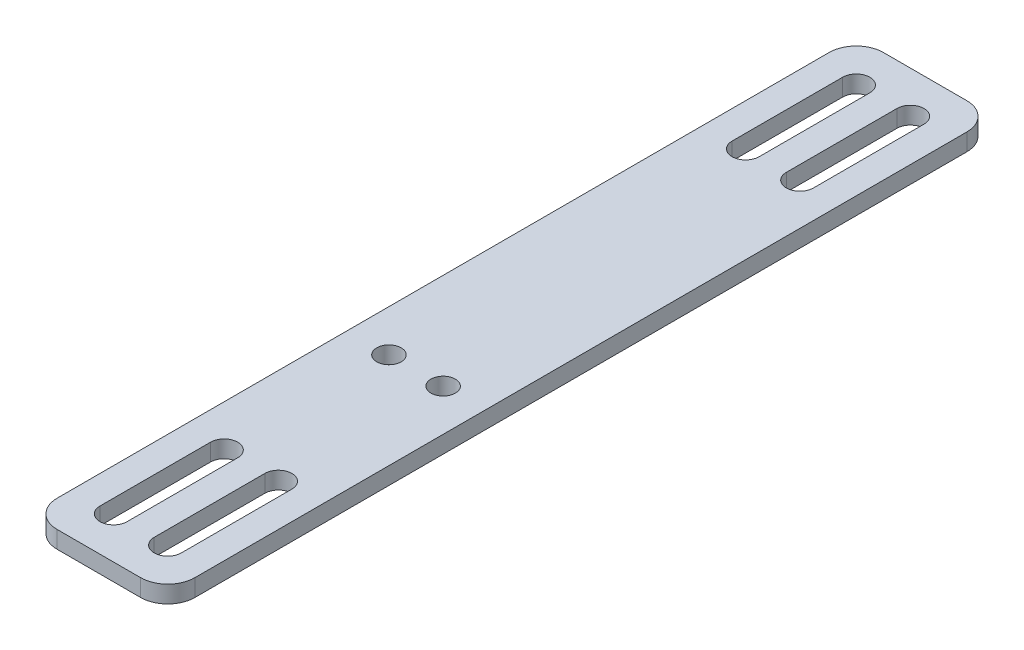
SolidWorks part; units mm, degrees
ref_plane "Front Plane" through (0, 0, 0) normal (0, 0, 1) x (1, 0, 0)
ref_plane "Top Plane" through (0, 0, 0) normal (0, 1, 0) x (1, 0, 0)
ref_plane "Right Plane" through (0, 0, 0) normal (1, 0, 0) x (0, 0, -1)
sketch "Sketch1" plane through (0, 0, 0) normal (0, 0, 1) x (1, 0, 0)
  line L0 (0, 1.5875) -> (0, -1.5875)
  line L1 (-12.7, 0) -> (12.7, 0) construction
  point P6 (0, 0)
  dimension "Width" = 25.4
  dimension "Thk" = 3.175
sketch "Sketch2" plane through (0, 0, 0) normal (1, 0, 0) x (0, 0, -1)
  line L0 (76.2, 0) -> (-76.2, 0)
  point P4 (0, 0)
  dimension "Length" = 152.4
sketch "Sketch3" plane through (0, 0, 0) normal (0, 0, 1) x (1, 0, 0)
  line L1 (12.7, 1.5875) -> (-12.7, 1.5875)
  line L2 (12.7, 1.5875) -> (12.7, -1.5875)
  line L3 (12.7, -1.5875) -> (-12.7, -1.5875)
  line L4 (-12.7, 1.5875) -> (-12.7, -1.5875)
  line L5 (12.7, 1.5875) -> (-12.7, -1.5875) construction
  line L6 (12.7, -1.5875) -> (-12.7, 1.5875) construction
  point P0 (0, 0)
extrude "Boss-Extrude1" add sketch "Sketch3" along normal up to vertex (76.2 mm away) and the other way up to vertex (76.2 mm away) up to point (0, 0, 76.2) other way up to point (0, 0, -76.2)
sketch "Sketch4" [suppressed] plane through (0, 1.5875, 0) normal (0, 1, 0) x (1, 0, 0)
  circle A2 centre (5, -17.7) radius 2.05
  circle A4 centre (-5, -17.7) radius 2.05
  dimension "D1" = 4.1
  dimension "D2" = 4.1
  dimension "D3" = 10
sketch "Sketch5" plane through (0, -1.5875, 0) normal (0, -1, 0) x (-1, 0, 0)
  line L7 (5, -48.1) -> (5, -68.5) construction
  line L8 (7.5, -48.1) -> (7.5, -68.5)
  line L9 (2.5, -48.1) -> (2.5, -68.5)
  line L10 (-5, -48.1) -> (-5, -68.5) construction
  line L11 (-2.5, -48.1) -> (-2.5, -68.5)
  line L12 (-7.5, -48.1) -> (-7.5, -68.5)
  line L13 (-12.7, -76.2) -> (12.7, -76.2) construction
  line L14 (12.7, -76.2) -> (12.7, 76.2) construction
  arc A2 (7.5, -48.1) -> (2.5, -48.1) centre (5, -48.1) ccw
  arc A3 (2.5, -68.5) -> (7.5, -68.5) centre (5, -68.5) ccw
  arc A4 (-2.5, -48.1) -> (-7.5, -48.1) centre (-5, -48.1) ccw
  arc A5 (-7.5, -68.5) -> (-2.5, -68.5) centre (-5, -68.5) ccw
  point P18 (5, -58.3)
  point P23 (-5, -58.3)
  dimension "D6" = 2.5
  dimension "D7" = 2.5
  dimension "D8" = 20.4
  dimension "D1" = 25.4
  dimension "D3" = 7.7
  dimension "D4" = 7.7
  dimension "D2" = 10
extrude "Cut-Extrude2" cut sketch "Sketch5" against normal up to surface (3.175 mm away) contours L12 A5 L11 A4 | L9 A3 L8 A2 up to face at (0, 1.5875, 0)
mirror "Mirror1" about plane through (0, 0, 0) normal (0, 0, 1) of "Cut-Extrude2"
fillet "Fillet1" radius 5 4 edges at (-12.7, 0, 76.2) (12.7, 0, 76.2) (-12.7, 0, -76.2) (12.7, 0, -76.2)
hole_wizard "M4 Clearance Hole1" positions "Sketch8" profile "Sketch9" hole size "M4" standard "ANSI Metric" end condition through all
sketch "Sketch8" plane through (0, 1.5875, 0) normal (0, 1, 0) x (1, 0, 0)
  line L0 (-12.7, -71.2) -> (-12.7, 71.2) construction
  point P0 (5, -17.7)
  point P2 (-5, -17.7)
  dimension "D1" = 10
  dimension "D2" = 7.7
  dimension "D3" = 17.7
sketch "Sketch9" plane through (5, 1.5875, 17.7) normal (1, 0, 0) x (0, 0, 1)
  line L0 (0, 0) -> (0, 3.175)
  line L1 (0, 3.175) -> (2.25, 3.175)
  line L2 (2.25, 3.175) -> (2.25, 0)
  line L5 (2.25, 0) -> (0, 0)
  line L11 (0, -6.35) -> (0, 107.95) construction
  dimension "Thru Hole Dia." = 4.5
  dimension "Thru Hole Depth" = 3.175
equation "\"D7@Sketch5\"=\"D6@Sketch5\""
equation "\"D4@Sketch5\"=\"D3@Sketch5\""
equation "\"D2@Sketch5\"=\"D1@Sketch5\"-2*\"D3@Sketch5\""
